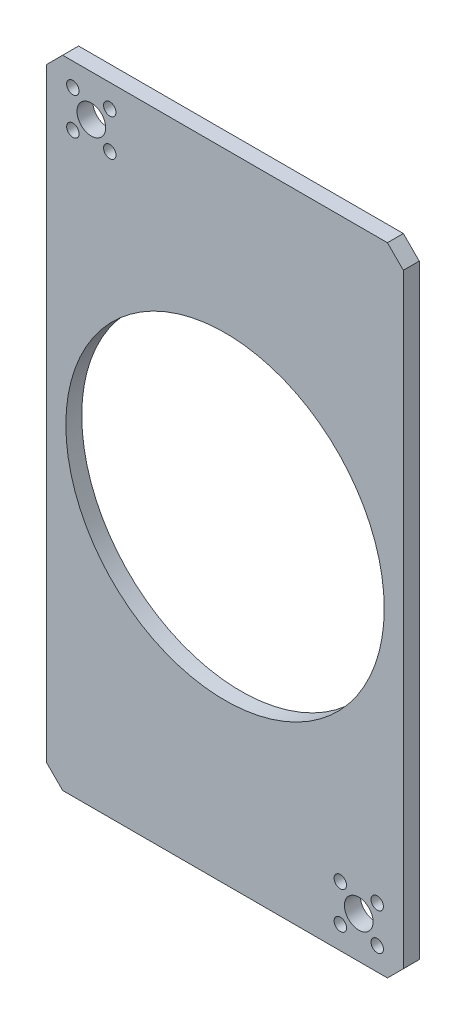
SolidWorks part; units mm, degrees
material "Beech"
ref_plane "Front Plane" through (0, 0, 0) normal (0, 0, 1) x (1, 0, 0)
ref_plane "Top Plane" through (0, 0, 0) normal (0, 1, 0) x (1, 0, 0)
ref_plane "Right Plane" through (0, 0, 0) normal (1, 0, 0) x (0, 0, -1)
sketch "Sketch1" plane through (0, 0, 0) normal (0, 0, 1) x (1, 0, 0)
  line L1 (-56, -100) -> (56, -100)
  line L2 (-56, -100) -> (-56, 100)
  line L3 (-56, 100) -> (56, 100)
  line L4 (56, -100) -> (56, 100)
  line L5 (-56, -100) -> (56, 100) construction
  line L6 (-56, 100) -> (56, -100) construction
  point P0 (0, 0)
  dimension "D1" = 112
  dimension "D2" = 200
extrude "Boss-Extrude1" add sketch "Sketch1" along normal blind 5
sketch "Sketch2" [suppressed] plane through (0, 0, 0) normal (0, 0, -1) x (-1, 0, 0)
  line L0 (61, 200) -> (61, -200) construction
  line L1 (-61, 314.7216) -> (-204.3993, 314.7216)
  line L2 (-61, 314.7216) -> (-61, -251.9618)
  line L3 (-61, -251.9618) -> (-204.3993, -251.9618)
  line L4 (-204.3993, 314.7216) -> (-204.3993, -251.9618)
  line L6 (61, 279.3211) -> (244.4765, 279.3211)
  line L7 (61, 279.3211) -> (61, -295.1839)
  line L8 (61, -295.1839) -> (244.4765, -295.1839)
  line L9 (244.4765, 279.3211) -> (244.4765, -295.1839)
  line L10 (-61, -200) -> (-61, -140) construction
extrude "Cut-Extrude1" [suppressed] cut sketch "Sketch2" against normal through all
sketch "Sketch3" [suppressed] plane through (49, 0, 0) normal (1, 0, 0) x (0, 0, -1)
  circle A0 centre (-6.722, 55.3681) radius 5.3835
surface "Surface-Extrude1" [suppressed] sketch "Sketch3"
sketch "Sketch4" [suppressed] plane through (-49, 0, 0) normal (-1, 0, 0) x (0, 0, 1)
  line L1 (2, 80) -> (0, 80) construction
  line L2 (0, -80) -> (0, 80) construction
  point P0 (7.5, 76)
  dimension "D1" = 4
  dimension "D2" = 7.5
ref_axis "Axis1" [suppressed] through (-49, 76, 7.5) along (1, 0, 0)
sketch "Sketch5" [suppressed] plane through (0, 0, 0) normal (0, 0, -1) x (-1, 0, 0)
  line L0 (49, 80) -> (49, -80) construction
  line L1 (-49, 80) -> (49, 80)
  line L2 (-49, 80) -> (-49, 60.2594)
  line L3 (-49, 60.2594) -> (49, 60.2594)
  line L4 (49, 80) -> (49, 60.2594)
extrude "Cut-Extrude2" [suppressed] cut sketch "Sketch5" against normal blind 3
sketch "Sketch6" plane through (0, 0, 5) normal (0, 0, 1) x (1, 0, 0)
  line L0 (0, 0) -> (103.2002, 0) construction
  line L1 (-42, 87) -> (-42, 108.3319) construction
  line L2 (-42, 87) -> (-27.987, 87) construction
  line L3 (0, 0) -> (0, 138.3235) construction
  line L4 (42, 87) -> (27.987, 87) construction
  line L5 (42, 87) -> (42, 108.3319) construction
  line L6 (42, -87) -> (42, -108.3319) construction
  line L7 (42, -87) -> (27.987, -87) construction
  line L8 (-42, -87) -> (-27.987, -87) construction
  line L9 (-42, -87) -> (-42, -108.3319) construction
  circle A0 centre (-42, 87) radius 4.5
  circle A2 centre (-47.8, 92.8) radius 1.95
  circle A3 centre (-47.8, 81.2) radius 1.95
  circle A4 centre (-36.2, 81.2) radius 1.95
  circle A5 centre (-36.2, 92.8) radius 1.95
  circle A6 centre (36.2, 92.8) radius 1.95
  circle A7 centre (36.2, 81.2) radius 1.95
  circle A8 centre (47.8, 81.2) radius 1.95
  circle A9 centre (47.8, 92.8) radius 1.95
  circle A10 centre (42, 87) radius 4.5
  circle A11 centre (42, -87) radius 4.5
  circle A12 centre (47.8, -92.8) radius 1.95
  circle A13 centre (47.8, -81.2) radius 1.95
  circle A14 centre (36.2, -81.2) radius 1.95
  circle A15 centre (36.2, -92.8) radius 1.95
  circle A16 centre (-36.2, -92.8) radius 1.95
  circle A17 centre (-36.2, -81.2) radius 1.95
  circle A18 centre (-47.8, -81.2) radius 1.95
  circle A19 centre (-47.8, -92.8) radius 1.95
  circle A20 centre (-42, -87) radius 4.5
  circle A21 centre (-42, 87) radius 5.1 construction
  dimension "D1" = 9
  dimension "D3" = 3.9
extrude "Leandut_holes" cut sketch "Sketch6" against normal through all
chamfer "Chamfer1" distance 5 angle 45 4 edges at (-56, -100, 2.5) (56, -100, 2.5) (56, 100, 2.5) (-56, 100, 2.5)
sketch "Sketch7" plane through (0, 0, 5) normal (0, 0, 1) x (1, 0, 0)
  circle A0 centre (0, 0) radius 50
  dimension "D1" = 100
extrude "Cut-Extrude3" cut sketch "Sketch7" against normal through all
other "DeleteFace1" face at (-45.85, -81.2, 0) face at (-38.15, -81.2, 0) face at (-46.5, -87, 0) face at (-49.75, -92.8, 0) face at (-34.25, -92.8, 0) face at (38.15, 92.8, 0) face at (45.85, 92.8, 0) face at (37.5, 87, 0) face at (34.25, 81.2, 0) face at (49.75, 81.2, 0) and patch yes
